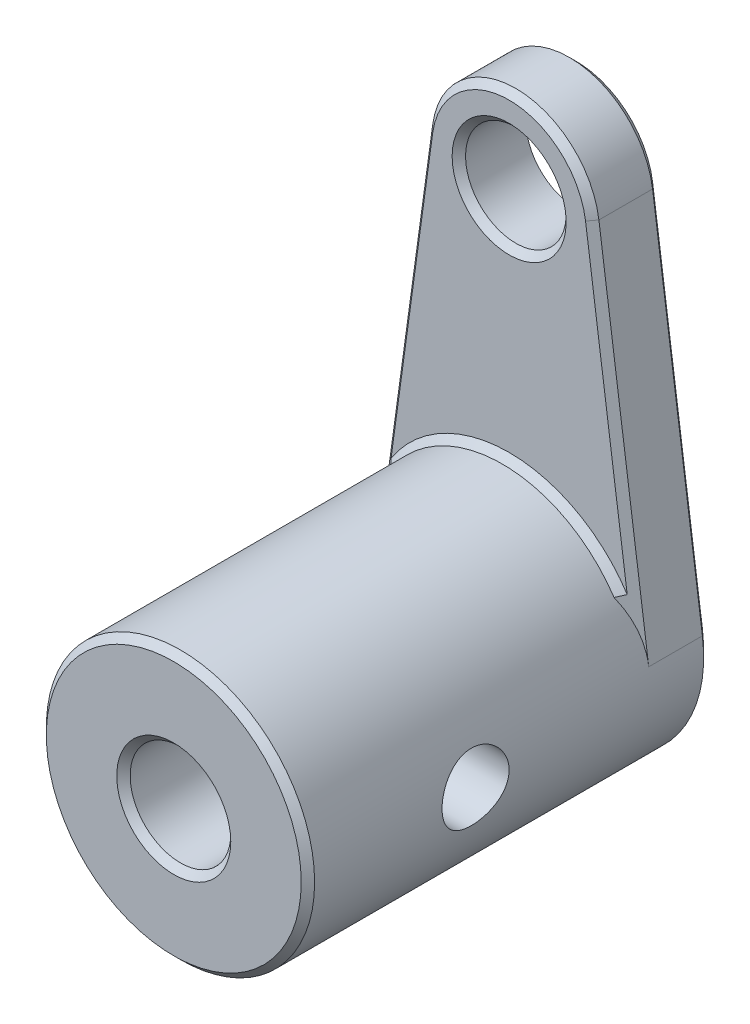
SolidWorks part; units mm, degrees
ref_plane "Front Plane" through (0, 0, 0) normal (0, 0, 1) x (1, 0, 0)
ref_plane "Top Plane" through (0, 0, 0) normal (0, 1, 0) x (1, 0, 0)
ref_plane "Right Plane" through (0, 0, 0) normal (1, 0, 0) x (0, 0, -1)
sketch "Sketch1" plane through (0, 0, 0) normal (0, 0, 1) x (1, 0, 0)
  line L0 (-2.4766, 11.3409) -> (-3.9626, 0.5455)
  line L1 (2.4766, 11.3409) -> (3.9626, 0.5455)
  arc A0 (3.9626, 0.5455) -> (-3.9626, 0.5455) centre (0, 0) cw
  arc A1 (-2.4766, 11.3409) -> (2.4766, 11.3409) centre (0, 11) cw
  circle A2 centre (0, 11) radius 1.5
  circle A3 centre (0, 0) radius 1.5
  dimension "D1" = 4
  dimension "D2" = 2.5
  dimension "D4" = 3
  dimension "D5" = 3
  dimension "D3" = 11
extrude "Boss-Extrude1" add sketch "Sketch1" along normal blind 2
sketch "Sketch2" plane through (0, 0, 2) normal (0, 0, 1) x (1, 0, 0)
  arc A0 (-3.9626, 0.5455) -> (3.9626, 0.5455) centre (0, 0) ccw construction
  circle A1 centre (0, 0) radius 4
  circle A2 centre (0, 0) radius 1.5 construction
  circle A3 centre (0, 0) radius 1.5
extrude "Boss-Extrude2" add sketch "Sketch2" along normal blind 10
sketch "Sketch3" plane through (0, 0, 0) normal (1, 0, 0) x (0, 0, -1)
  line L0 (-12, 4) -> (-12, -4) construction
  circle A0 centre (-7, 0) radius 1
  dimension "D1" = 2
  dimension "D2" = 5
extrude "Cut-Extrude1" cut sketch "Sketch3" against normal through all both and the other way through all
chamfer "Chamfer1" distance 0.2 angle 45 10 edges at (1.5, 0, 12) (3.2196, 5.9432, 0) (0, 13.5, 0) (0, -4, 0) (-3.2196, 5.9432, 0) (4, 0, 12) (1.5, 11, 2) (3.2196, 5.9432, 2) (-3.2196, 5.9432, 2) (0, 13.5, 2)
chamfer "Chamfer2" distance 0.2 angle 45 1 edges at (0, 4, 2)
sketch "Sketch4" plane through (0, 0, 2) normal (0, 0, 1) x (1, 0, 0)
  line L0 (0, 0) -> (0, 13.5) construction
  arc A0 (2.4766, 11.3409) -> (-2.4766, 11.3409) centre (0, 11) ccw construction
